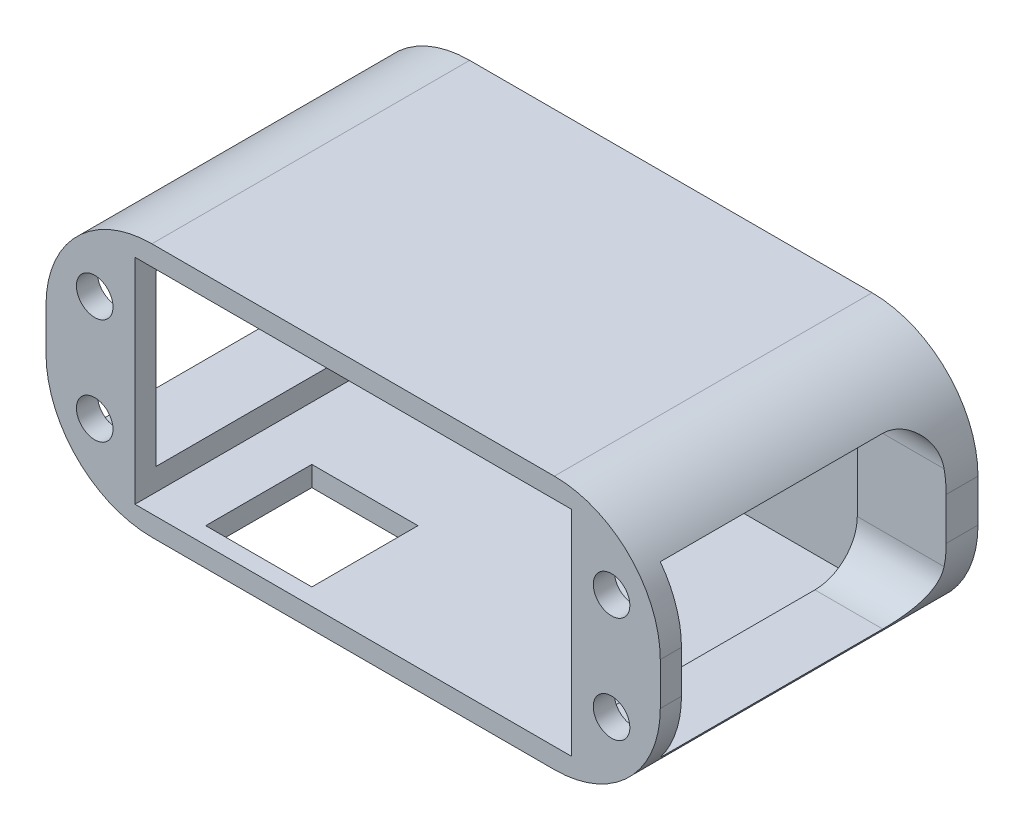
SolidWorks part; units mm, degrees
ref_plane "Front Plane" through (0, 0, 0) normal (0, 0, 1) x (1, 0, 0)
ref_plane "Top Plane" through (0, 0, 0) normal (0, 1, 0) x (1, 0, 0)
ref_plane "Right Plane" through (0, 0, 0) normal (1, 0, 0) x (0, 0, -1)
sketch "Sketch1" plane through (0, 0, 0) normal (0, 0, 1) x (1, 0, 0)
  line L1 (29, -12) -> (-29, -12)
  line L2 (29, -12) -> (29, 12)
  line L3 (29, 12) -> (-29, 12)
  line L4 (-29, -12) -> (-29, 12)
  line L5 (29, -12) -> (-29, 12) construction
  line L6 (29, 12) -> (-29, -12) construction
  point P0 (0, 0)
  dimension "D1" = 58
  dimension "D2" = 24
extrude "Boss-Extrude1" add sketch "Sketch1" against normal blind 30
sketch "Sketch8" plane through (0, 0, 0) normal (0, 0, 1) x (1, 0, 0)
  circle A0 centre (-24.4, 5) radius 1
  circle A1 centre (-24.4, -5) radius 1
  circle A2 centre (24.4, -5) radius 1
  circle A3 centre (24.4, 5) radius 1
  dimension "D1" = 2
  dimension "D2" = 2
  dimension "D3" = 2
  dimension "D4" = 2
hole_wizard "#8-32 Tapped Hole2" positions "3DSketch5" profile "Sketch11" tap size "#8-32" standard "ANSI Inch"
sketch3d "3DSketch5"
  point P0 (24.4, -5, 0)
  point P3 (24.4, 5, 0)
  point P6 (-24.4, -5, 0)
  point P9 (-24.4, 5, 0)
sketch "Sketch11" plane through (24.4, -5, 0) normal (1, 0, 0) x (0, -1, 0)
  line L0 (0, 0) -> (0, 13.0378)
  line L1 (0, 13.0378) -> (1.7272, 12)
  line L2 (1.7272, 12) -> (1.7272, 0)
  line L5 (1.7272, 0) -> (0, 0)
  line L10 (0, 13.0378) -> (-1.7272, 12) construction
  line L11 (0, -6.35) -> (0, 107.95) construction
  dimension "Tap Drill Dia." = 3.4544
  dimension "Tap Drill Depth" = 12
  dimension "Drill Angle" = 118
cosmetic thread "Hole Thread38" parameters "D1"=2.075, "D2"=4.1656
cosmetic thread "Hole Thread39" parameters "D1"=2.075, "D2"=4.1656
cosmetic thread "Hole Thread40" parameters "D1"=2.075, "D2"=4.1656
cosmetic thread "Hole Thread41" parameters "D1"=2.075, "D2"=4.1656
sketch "Sketch18" plane through (0, 0, 0) normal (0, 0, 1) x (1, 0, 0)
  line L1 (20.6, 10.1) -> (-20.6, 10.1)
  line L2 (20.6, 10.1) -> (20.6, -10.1)
  line L3 (20.6, -10.1) -> (-20.6, -10.1)
  line L4 (-20.6, 10.1) -> (-20.6, -10.1)
  line L5 (20.6, 10.1) -> (-20.6, -10.1) construction
  line L6 (20.6, -10.1) -> (-20.6, 10.1) construction
  point P0 (0, 0)
  dimension "D1" = 41.2
  dimension "D2" = 20.2
extrude "Cut-Extrude6" cut sketch "Sketch18" against normal blind 28
sketch "Sketch22" plane through (0, 0, -30) normal (0, 0, -1) x (-1, 0, 0)
  circle A0 centre (10.5, 0) radius 1.505
  dimension "D1" = 3.01
extrude "Cut-Extrude9" cut sketch "Sketch22" against normal blind 2
sketch "Sketch24" plane through (0, -10.1, 0) normal (0, 1, 0) x (1, 0, 0)
  line L1 (-15.51, 1.59) -> (-5.49, 1.59)
  line L2 (-15.51, 1.59) -> (-15.51, 11.61)
  line L3 (-15.51, 11.61) -> (-5.49, 11.61)
  line L4 (-5.49, 1.59) -> (-5.49, 11.61)
  line L5 (-15.51, 1.59) -> (-5.49, 11.61) construction
  line L6 (-15.51, 11.61) -> (-5.49, 1.59) construction
  point P0 (-10.5, 6.6)
  dimension "D1" = 10.02
  dimension "D2" = 10.02
extrude "Cut-Extrude11" cut sketch "Sketch24" against normal blind 2
fillet "Fillet1" radius 10 1 edges at (-29, 12, -15)
fillet "Fillet2" radius 10 1 edges at (29, 12, -15)
fillet "Fillet3" radius 10 1 edges at (29, -12, -15)
fillet "Fillet4" radius 10 1 edges at (-29, -12, -15)
sketch "Sketch25" plane through (-29, 0, 0) normal (-1, 0, 0) x (0, 0, 1)
  line L0 (-30, 2) -> (-30, -2) construction
  line L1 (-27, 8) -> (-2, 8)
  line L2 (-27, 8) -> (-27, -8)
  line L3 (-27, -8) -> (-2, -8)
  line L4 (-2, 8) -> (-2, -8)
  line L5 (0, 2) -> (0, -2) construction
  line L6 (-30, 12) -> (0, 12) construction
  line L7 (0, -12) -> (-30, -12) construction
  dimension "D1" = 3
  dimension "D2" = 2
  dimension "D3" = 4
  dimension "D4" = 4
extrude "Cut-Extrude12" cut sketch "Sketch25" against normal blind 10
sketch "Sketch27" plane through (29, 0, 0) normal (1, 0, 0) x (0, 0, -1)
  line L0 (0, -2) -> (0, 2) construction
  line L1 (2, 8) -> (27, 8)
  line L2 (2, 8) -> (2, -8)
  line L3 (2, -8) -> (27, -8)
  line L4 (27, 8) -> (27, -8)
  line L5 (30, -2) -> (30, 2) construction
  line L6 (0, 12) -> (30, 12) construction
  line L7 (30, -12) -> (0, -12) construction
  dimension "D1" = 2
  dimension "D2" = 3
  dimension "D3" = 4
  dimension "D4" = 4
extrude "Cut-Extrude13" cut sketch "Sketch27" against normal blind 10
fillet "Fillet6" radius 4 1 edges at (23.8, -8, -27)
fillet "Fillet7" radius 4 1 edges at (23.8, 8, -27)
fillet "Fillet8" radius 4 1 edges at (-23.8, -8, -27)
fillet "Fillet9" radius 4 1 edges at (-23.8, 8, -27)
